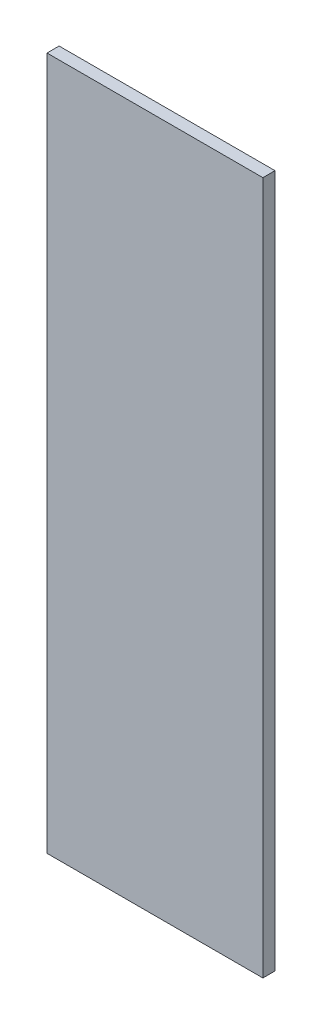
SolidWorks part; units mm, degrees
material "ABS"
ref_plane "X-Y Datum" through (0, 0, 0) normal (0, 0, 1) x (1, 0, 0)
ref_plane "X-Z Datum" through (0, 0, 0) normal (0, 1, 0) x (1, 0, 0)
ref_plane "Y-Z Datum" through (0, 0, 0) normal (1, 0, 0) x (0, 0, -1)
sketch "Sketch1" plane through (0, 0, 0) normal (0, 0, 1) x (1, 0, 0)
  line L1 (-28.275, 90.775) -> (28.275, 90.775)
  line L2 (-28.275, 90.775) -> (-28.275, -90.775)
  line L3 (-28.275, -90.775) -> (28.275, -90.775)
  line L4 (28.275, 90.775) -> (28.275, -90.775)
  line L5 (-28.275, 90.775) -> (28.275, -90.775) construction
  line L6 (-28.275, -90.775) -> (28.275, 90.775) construction
  point P0 (0, 0)
  dimension "D1" = 56.55
  dimension "D2" = 181.55
extrude "Boss-Extrude1" add sketch "Sketch1" along normal blind 3.175
